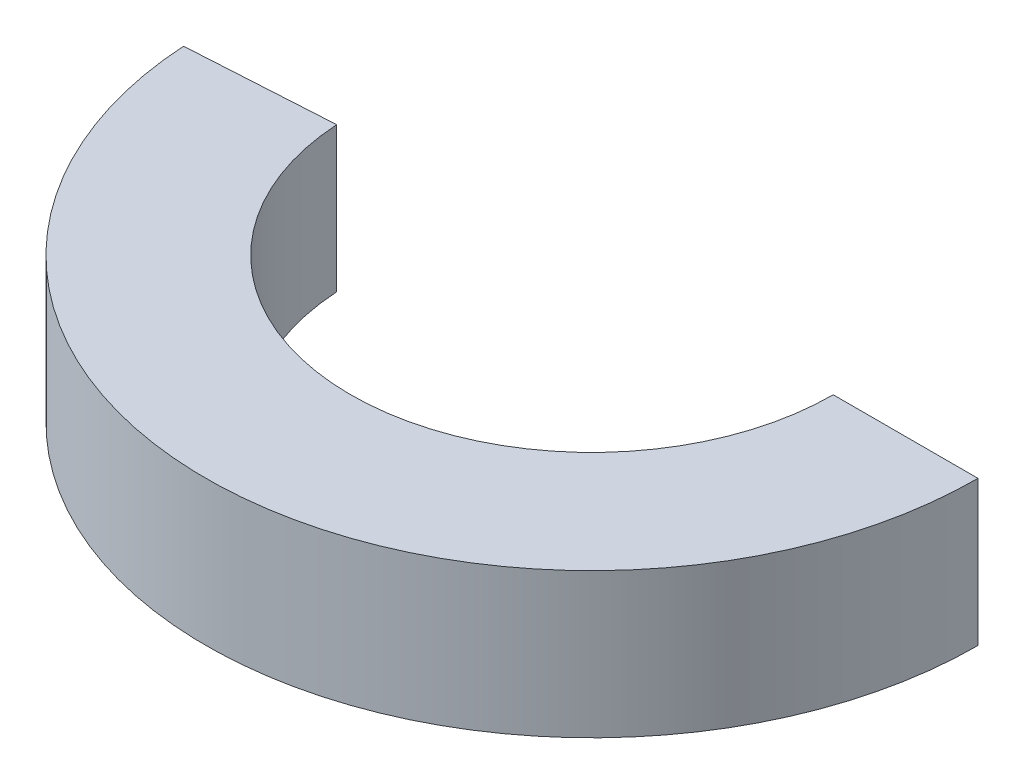
SolidWorks part; units mm, degrees
material "Custom Plastic"
ref_plane "Front Plane" through (0, 0, 0) normal (0, 0, 1) x (1, 0, 0)
ref_plane "Top Plane" through (0, 0, 0) normal (0, 1, 0) x (1, 0, 0)
ref_plane "Right Plane" through (0, 0, 0) normal (1, 0, 0) x (0, 0, -1)
sketch "Sketch1" plane through (0, 0, 0) normal (0, 1, 0) x (1, 0, 0)
  line L0 (-39.9292, -2.3792) -> (0, 0)
  line L1 (0, 0) -> (40, 0)
  circle A0 centre (0, 0) radius 25
  circle A1 centre (0, 0) radius 40
  dimension "D1" = 15
  dimension "D2" = 80
  dimension "D3" = 176.59
extrude "Boss-Extrude1" add sketch "Sketch1" along normal blind 15 contours L0 A1 L1 A0 region at (-32.3893, 0, 2.8253)
